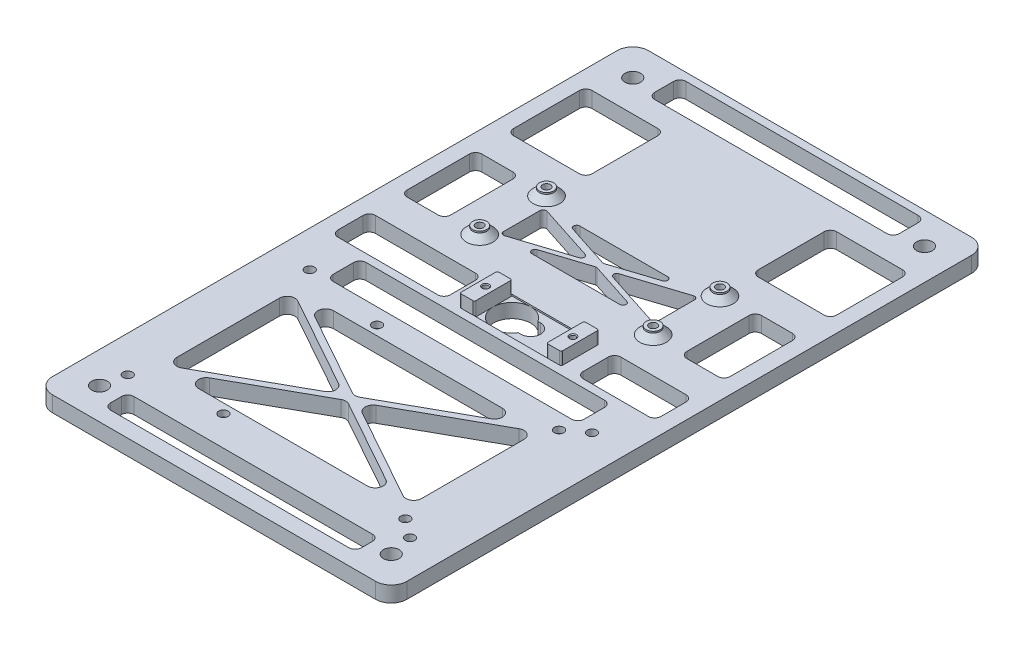
SolidWorks part; units mm, degrees
ref_plane "Front Plane" through (0, 0, 0) normal (0, 0, 1) x (1, 0, 0)
ref_plane "Top Plane" through (0, 0, 0) normal (0, 1, 0) x (1, 0, 0)
ref_plane "Right Plane" through (0, 0, 0) normal (1, 0, 0) x (0, 0, -1)
sketch "Sketch1" plane through (0, 0, 0) normal (0, 1, 0) x (1, 0, 0)
  line L0 (-56.5, -95) -> (-56.5, 95)
  line L1 (-46.5, -85) -> (46.5, -85) construction
  line L2 (-46.5, -85) -> (-46.5, 85) construction
  line L3 (-46.5, 85) -> (46.5, 85) construction
  line L4 (46.5, -85) -> (46.5, 85) construction
  line L5 (-46.5, -85) -> (46.5, 85) construction
  line L6 (-46.5, 85) -> (46.5, -85) construction
  line L7 (-56.5, 95) -> (56.5, 95)
  line L8 (56.5, -95) -> (56.5, 95)
  line L9 (-56.5, -95) -> (56.5, -95)
  circle A0 centre (46.5, 85) radius 2.5
  circle A1 centre (-46.5, 85) radius 2.5
  circle A2 centre (-46.5, -85) radius 2.5
  circle A3 centre (46.5, -85) radius 2.5
  point P0 (0, 0)
  dimension "D3" = 5
  dimension "D1" = 170
  dimension "D2" = 93
  dimension "D4" = 10
extrude "Boss-Extrude1" add sketch "Sketch1" along normal blind 5
fillet "Fillet1" radius 5 4 edges at (-56.5, 2.5, 95) (-56.5, 2.5, -95) (56.5, 2.5, -95) (56.5, 2.5, 95)
sketch "Sketch2" plane through (0, 5, 0) normal (0, 1, 0) x (1, 0, 0)
  line L0 (-39, -24) -> (-39, -73) construction
  line L1 (-39, -24) -> (39, -24) construction
  line L2 (-39, -20.5) -> (39, -20.5) construction
  line L3 (42.5, -48.5) -> (-39, -48.5) construction
  line L4 (-42.5, -24) -> (-42.5, -73) construction
  line L5 (42.5, -24) -> (42.5, -73) construction
  line L6 (-39, -76.5) -> (39, -76.5) construction
  line L7 (0, -20.5) -> (0, -1.8528) construction
  line L8 (-51.5, -95) -> (51.5, -95) construction
  circle A0 centre (39, -24) radius 1.5
  circle A1 centre (39, -73) radius 1.5
  arc A2 (-39, -20.5) -> (-42.5, -24) centre (-39, -24) ccw construction
  arc A3 (-39, -76.5) -> (-42.5, -73) centre (-39, -73) cw construction
  arc A4 (42.5, -24) -> (39, -20.5) centre (39, -24) ccw construction
  arc A5 (42.5, -73) -> (39, -76.5) centre (39, -73) cw construction
  circle A6 centre (-19, -24) radius 1.5
  circle A7 centre (-19, -73) radius 1.5
  point P14 (1.75, -48.5)
  dimension "D1" = 3
  dimension "D2" = 49
  dimension "D3" = 85
  dimension "D4" = 56
  dimension "D5" = 58
  dimension "D6" = 18.5
extrude "Cut-Extrude1" cut sketch "Sketch2" against normal blind 10
sketch "Sketch3" plane through (0, 5, 0) normal (0, 1, 0) x (1, 0, 0)
  line L0 (-45, -80) -> (45, -80) construction
  line L1 (-47.5, -77.5) -> (-47.5, -19.5) construction
  line L2 (-45, -17) -> (45, -17) construction
  line L3 (47.5, -77.5) -> (47.5, -19.5) construction
  line L4 (-47.5, -80) -> (47.5, -17) construction
  line L5 (-47.5, -17) -> (47.5, -80) construction
  line L6 (-51.5, -95) -> (51.5, -95) construction
  circle A0 centre (45, -19.5) radius 1.5
  circle A1 centre (45, -77.5) radius 1.5
  circle A2 centre (-45, -19.5) radius 1.5
  circle A3 centre (-45, -77.5) radius 1.5
  arc A4 (-47.5, -19.5) -> (-45, -17) centre (-45, -19.5) cw construction
  arc A5 (-45, -80) -> (-47.5, -77.5) centre (-45, -77.5) cw construction
  arc A6 (45, -80) -> (47.5, -77.5) centre (45, -77.5) ccw construction
  arc A7 (45, -17) -> (47.5, -19.5) centre (45, -19.5) cw construction
  point P0 (0, -48.5)
  dimension "D3" = 2.5
  dimension "D1" = 95
  dimension "D2" = 63
  dimension "D4" = 15
extrude "Cut-Extrude2" cut sketch "Sketch3" against normal blind 10
sketch "Sketch5" plane through (0, 5, 0) normal (0, 1, 0) x (1, 0, 0)
  line L1 (-38, -90) -> (38, -90)
  line L2 (-40, -88) -> (-40, -84.5)
  line L3 (-38, -82.5) -> (38, -82.5)
  line L4 (40, -88) -> (40, -84.5)
  line L5 (-40, -90) -> (40, -82.5) construction
  line L6 (-40, -82.5) -> (40, -90) construction
  circle A2 centre (-46.5, -85) radius 2.5 construction
  arc A3 (-38, -90) -> (-40, -88) centre (-38, -88) cw
  arc A4 (-40, -84.5) -> (-38, -82.5) centre (-38, -84.5) cw
  arc A5 (38, -82.5) -> (40, -84.5) centre (38, -84.5) cw
  arc A6 (38, -90) -> (40, -88) centre (38, -88) ccw
  point P0 (0, -86.25)
  dimension "D3" = 2
  dimension "D1" = 7.5
  dimension "D2" = 80
extrude "Cut-Extrude4" cut sketch "Sketch5" against normal blind 10
sketch "Sketch21" plane through (0, 5, 0) normal (0, 1, 0) x (1, 0, 0)
  line L4 (5.975, 2.875) -> (5.122, 2.875) construction
  line L5 (5.975, -2.875) -> (5.122, -2.875) construction
  line L6 (5.975, -3.125) -> (5.122, -3.125)
  line L7 (5.975, 3.125) -> (5.122, 3.125)
  arc A8 (4.9085, 2.9948) -> (4.9085, -2.9948) centre (0, 0) ccw construction
  arc A11 (5.975, -2.875) -> (5.975, 2.875) centre (5.975, 0) ccw construction
  arc A12 (4.9085, 2.9948) -> (5.122, 2.875) centre (5.122, 3.125) ccw construction
  arc A13 (5.122, -2.875) -> (4.9085, -2.9948) centre (5.122, -3.125) ccw construction
  arc A14 (5.122, 3.125) -> (5.122, -3.125) centre (0, 0) ccw
  arc A15 (5.122, -3.125) -> (5.122, -3.125) centre (5.122, -3.125) ccw
  arc A16 (5.975, -3.125) -> (5.975, 3.125) centre (5.975, 0) ccw
  arc A17 (5.122, 3.125) -> (5.122, 3.125) centre (5.122, 3.125) ccw
  dimension "D2" = 2.875
  dimension "D3" = 5.75
  dimension "D4" = 0.25
  dimension "D5" = 0.25
  dimension "D1" = 5.975
extrude "Cut-Extrude16" cut sketch "Sketch21" against normal through all
sketch "Sketch22" plane through (0, 5, 0) normal (0, 1, 0) x (1, 0, 0)
  line L0 (-6, 6) -> (-6, -6)
  line L1 (-6, 6) -> (17, 6)
  line L2 (-6, -6) -> (17, -6)
  line L3 (17, 6) -> (17, -6)
  arc A0 (5.122, 3.125) -> (5.122, -3.125) centre (0, 0) ccw construction
  dimension "D1" = 23
extrude "Cut-Extrude17" cut sketch "Sketch22" against normal blind 0.5
sketch "Sketch23" plane through (0, 5, 0) normal (0, 1, 0) x (1, 0, 0)
  line L0 (-6, 6) -> (-6, -6)
  line L1 (-6, 6) -> (-10.675, 6)
  line L2 (-6, -6) -> (-10.675, -6)
  line L3 (-10.675, 6) -> (-10.675, -6)
  line L4 (5.5, -6) -> (5.5, 6) construction
  line L5 (-6, -6) -> (17, -6) construction
  line L6 (17, 6) -> (-6, 6) construction
  line L7 (17, -6) -> (21.675, -6)
  line L8 (21.675, 6) -> (21.675, -6)
  line L9 (17, 6) -> (21.675, 6)
  line L10 (17, 6) -> (17, -6)
  circle A0 centre (-8.4, 0) radius 0.875
  circle A1 centre (19.4, 0) radius 0.875
  dimension "D2" = 1.75
  dimension "D1" = 4.675
  dimension "D3" = 2.4
extrude "Boss-Extrude5" add sketch "Sketch23" along normal blind 4
sketch "Sketch24" plane through (0, 5, 0) normal (0, 1, 0) x (1, 0, 0)
  circle A0 centre (19.4, 0) radius 0.875 construction
  circle A1 centre (-8.4, 0) radius 0.875 construction
  circle A2 centre (19.4, 0) radius 0.875
  circle A3 centre (-8.4, 0) radius 0.875
extrude "Cut-Extrude18" cut sketch "Sketch24" against normal blind 1.5
sketch "Sketch9" plane through (0, 5, 0) normal (0, 1, 0) x (1, 0, 0)
  line L0 (-48.1787, 10) -> (48.1787, 10)
  line L1 (-50, 11.8213) -> (-50, 38.1787)
  line L2 (-48.1787, 40) -> (48.1787, 40)
  line L3 (50, 11.8213) -> (50, 38.1787)
  line L4 (-50, 10) -> (50, 40) construction
  line L5 (-50, 40) -> (50, 10) construction
  arc A0 (48.1787, 40) -> (50, 38.1787) centre (48.1787, 38.1787) cw
  arc A1 (48.1787, 10) -> (50, 11.8213) centre (48.1787, 11.8213) ccw
  arc A2 (-48.1787, 10) -> (-50, 11.8213) centre (-48.1787, 11.8213) cw
  arc A3 (-50, 38.1787) -> (-48.1787, 40) centre (-48.1787, 38.1787) cw
  point P0 (0, 25)
  dimension "D4" = 1.8213
  dimension "D1" = 30
  dimension "D2" = 100
  dimension "D3" = 25
sketch "Sketch12" plane through (0, 5, 0) normal (0, 1, 0) x (1, 0, 0)
  line L1 (-51.5, 75) -> (-26.5, 75)
  line L2 (-51.5, 75) -> (-51.5, 50)
  line L3 (-51.5, 50) -> (-26.5, 50)
  line L4 (-26.5, 75) -> (-26.5, 50)
  line L6 (0, 0) -> (0, -22.2555) construction
  line L7 (26.5, 75) -> (26.5, 50)
  line L8 (51.5, 50) -> (26.5, 50)
  line L9 (51.5, 75) -> (51.5, 50)
  line L10 (51.5, 75) -> (26.5, 75)
  line L11 (-56.5, 90) -> (-56.5, -90) construction
  dimension "D1" = 25
  dimension "D2" = 25
  dimension "D3" = 50
  dimension "D4" = 5
extrude "Cut-Extrude9" cut sketch "Sketch12" against normal through all
sketch "Sketch15" plane through (0, 5, 0) normal (0, 1, 0) x (1, 0, 0)
  line L1 (-51.5, 6) -> (-15.675, 6)
  line L2 (-51.5, 6) -> (-51.5, -6)
  line L3 (-51.5, -6) -> (-15.675, -6)
  line L4 (-15.675, 6) -> (-15.675, -6)
  line L6 (-56.5, 90) -> (-56.5, -90) construction
  line L9 (26.675, 6) -> (51.5, 6)
  line L10 (26.675, 6) -> (26.675, -6)
  line L11 (26.675, -6) -> (51.5, -6)
  line L12 (51.5, 6) -> (51.5, -6)
  line L13 (56.5, -90) -> (56.5, 90) construction
  line L15 (17, 6) -> (-6, 6) construction
  line L16 (-6, -6) -> (17, -6) construction
  line L17 (21.675, -6) -> (21.675, 6) construction
  line L18 (-10.675, 6) -> (-10.675, -6) construction
  dimension "D1" = 5
  dimension "D2" = 5
  dimension "D3" = 5
  dimension "D4" = 5
extrude "Cut-Extrude11" cut sketch "Sketch15" against normal up to next
fillet "Fillet3" radius 2 16 edges at (-51.5, 2.5, 6) (-51.5, 2.5, -6) (-15.675, 2.5, -6) (-15.675, 2.5, 6) (51.5, 2.5, -6) (26.675, 2.5, -6) (26.675, 2.5, 6) (51.5, 2.5, 6) (51.5, 2.5, -50) (51.5, 2.5, -75) (26.5, 2.5, -50) (26.5, 2.5, -75) (-26.5, 2.5, -50) (-51.5, 2.5, -50) (-51.5, 2.5, -75) (-26.5, 2.5, -75)
sketch "Sketch16" plane through (0, 0, 0) normal (0, -1, 0) x (1, 0, 0)
  line L0 (-42, 64.8229) -> (-42, 32.1771)
  line L1 (-42.5, 70.5) -> (36.5, 70.5) construction
  line L2 (-42.5, 70.5) -> (-42.5, 26.5) construction
  line L3 (-42.5, 26.5) -> (36.5, 26.5) construction
  line L4 (36.5, 70.5) -> (36.5, 26.5) construction
  line L5 (-42.5, 70.5) -> (36.5, 26.5) construction
  line L6 (-42.5, 26.5) -> (36.5, 70.5) construction
  line L7 (-38.2835, 29.993) -> (-8.9766, 46.3159)
  line L8 (-8.9766, 50.6841) -> (-38.2835, 67.007)
  line L9 (-31.1371, 31.6841) -> (-4.2165, 46.6778)
  line L10 (-1.7835, 46.6778) -> (25.1371, 31.6841)
  line L11 (23.9206, 27) -> (-29.9206, 27)
  line L12 (-3, 48.5) -> (-3, 70.5) construction
  line L13 (-3, 48.5) -> (36.5, 48.5) construction
  line L14 (32.2835, 29.993) -> (2.9766, 46.3159)
  line L15 (36, 64.8229) -> (36, 32.1771)
  line L16 (2.9766, 50.6841) -> (32.2835, 67.007)
  line L17 (-1.7835, 50.3222) -> (25.1371, 65.3159)
  line L18 (-31.1371, 65.3159) -> (-4.2165, 50.3222)
  line L19 (23.9206, 70) -> (-29.9206, 70)
  line L20 (-33.5875, -28) -> (-33.5875, -6) construction
  line L26 (-27.65, -38.65) -> (27.65, -38.65) construction
  line L27 (-27.65, -38.65) -> (-27.65, -17.35) construction
  line L28 (-49.5, -6) -> (-17.675, -6) construction
  line L29 (-33.5875, -28) -> (-33.5875, -50) construction
  line L30 (51.5, -95) -> (-51.5, -95) construction
  line L31 (-37, -82.5) -> (37, -82.5)
  line L32 (-39, -84.5) -> (-39, -90.5)
  line L33 (-37, -92.5) -> (37, -92.5)
  line L34 (39, -84.5) -> (39, -90.5)
  line L35 (-39, -82.5) -> (39, -92.5) construction
  line L36 (-39, -92.5) -> (39, -82.5) construction
  line L37 (-28.5, -75) -> (-49.5, -75) construction
  line L44 (-49.5, -50) -> (-28.5, -50) construction
  line L63 (-27.65, -17.35) -> (27.65, -17.35) construction
  line L64 (27.65, -38.65) -> (27.65, -17.35) construction
  line L65 (-27.65, -38.65) -> (27.65, -17.35) construction
  line L66 (-27.65, -17.35) -> (27.65, -38.65) construction
  circle A0 centre (-45, 77.5) radius 1.5 construction
  circle A1 centre (39, 73) radius 1.5 construction
  circle A2 centre (39, 24) radius 1.5 construction
  circle A3 centre (-19, 73) radius 1.5 construction
  arc A4 (23.9206, 27) -> (25.1371, 31.6841) centre (23.9206, 29.5) ccw
  arc A5 (-1.7835, 46.6778) -> (-4.2165, 46.6778) centre (-3, 44.4938) ccw
  arc A6 (-29.9206, 27) -> (-31.1371, 31.6841) centre (-29.9206, 29.5) cw
  arc A7 (-42, 32.1771) -> (-38.2835, 29.993) centre (-39.5, 32.1771) ccw
  arc A8 (-8.9766, 46.3159) -> (-8.9766, 50.6841) centre (-10.193, 48.5) ccw
  arc A9 (-38.2835, 67.007) -> (-42, 64.8229) centre (-39.5, 64.8229) ccw
  arc A10 (36, 32.1771) -> (32.2835, 29.993) centre (33.5, 32.1771) cw
  arc A11 (2.9766, 46.3159) -> (2.9766, 50.6841) centre (4.193, 48.5) cw
  arc A12 (32.2835, 67.007) -> (36, 64.8229) centre (33.5, 64.8229) cw
  arc A13 (-1.7835, 50.3222) -> (-4.2165, 50.3222) centre (-3, 52.5062) cw
  arc A14 (23.9206, 70) -> (25.1371, 65.3159) centre (23.9206, 67.5) cw
  arc A15 (-29.9206, 70) -> (-31.1371, 65.3159) centre (-29.9206, 67.5) ccw
  circle A16 centre (-46.5, -85) radius 2.5 construction
  circle A17 centre (46.5, -85) radius 2.5 construction
  arc A30 (-39, -90.5) -> (-37, -92.5) centre (-37, -90.5) ccw
  arc A31 (37, -92.5) -> (39, -90.5) centre (37, -90.5) ccw
  arc A32 (39, -84.5) -> (37, -82.5) centre (37, -84.5) ccw
  arc A33 (-37, -82.5) -> (-39, -84.5) centre (-37, -84.5) ccw
  circle A34 centre (-27.65, -17.35) radius 1.25
  circle A35 centre (27.65, -17.35) radius 1.25
  circle A36 centre (27.65, -38.65) radius 1.25
  circle A37 centre (-27.65, -38.65) radius 1.25
  point P4 (-3, 48.5)
  point P52 (0, -28)
  point P69 (0, -87.5)
  dimension "D3" = 2.5
  dimension "D4" = 2.5
  dimension "D11" = 2.5
  dimension "D18" = 2
  dimension "D19" = 2
  dimension "D20" = 2.5
  dimension "D1" = 2.5
  dimension "D2" = 2.5
  dimension "D5" = 1
  dimension "D6" = 1
  dimension "D7" = 1
  dimension "D8" = 1
  dimension "D9" = 1
  dimension "D10" = 1
  dimension "D12" = 55.3
  dimension "D13" = 21.3
  dimension "D14" = 2.5
  dimension "D15" = 7.5
  dimension "D16" = 7.5
  dimension "D17" = 7.5
extrude "Cut-Extrude12" cut sketch "Sketch16" against normal up to next
sketch "Sketch17" plane through (0, 5, 0) normal (0, 1, 0) x (1, 0, 0)
  line L0 (0, 0) -> (0, 50000) construction
  line L1 (-39.65, 39.9) -> (-49.5, 39.9)
  line L2 (-37.65, 37.9) -> (-37.65, 18.1)
  line L3 (-39.65, 16.1) -> (-49.5, 16.1)
  line L4 (-51.5, 37.9) -> (-51.5, 18.1)
  line L5 (-37.65, 39.9) -> (-51.5, 16.1) construction
  line L6 (-37.65, 16.1) -> (-51.5, 39.9) construction
  line L7 (-51.5, 73) -> (-51.5, 52) construction
  line L8 (39.65, 16.1) -> (49.5, 16.1)
  line L9 (51.5, 37.9) -> (51.5, 18.1)
  line L10 (39.65, 39.9) -> (49.5, 39.9)
  line L11 (37.65, 37.9) -> (37.65, 18.1)
  circle A0 centre (-27.65, 17.35) radius 1.25 construction
  circle A1 centre (-27.65, 38.65) radius 1.25 construction
  arc A2 (-51.5, 18.1) -> (-49.5, 16.1) centre (-49.5, 18.1) ccw
  arc A3 (-39.65, 16.1) -> (-37.65, 18.1) centre (-39.65, 18.1) ccw
  arc A4 (-37.65, 37.9) -> (-39.65, 39.9) centre (-39.65, 37.9) ccw
  arc A5 (-49.5, 39.9) -> (-51.5, 37.9) centre (-49.5, 37.9) ccw
  arc A6 (51.5, 18.1) -> (49.5, 16.1) centre (49.5, 18.1) cw
  arc A7 (49.5, 39.9) -> (51.5, 37.9) centre (49.5, 37.9) cw
  arc A8 (39.65, 16.1) -> (37.65, 18.1) centre (39.65, 18.1) cw
  arc A9 (37.65, 37.9) -> (39.65, 39.9) centre (39.65, 37.9) cw
  point P4 (-44.575, 28)
  dimension "D2" = 2
  dimension "D1" = 10
extrude "Cut-Extrude13" cut sketch "Sketch17" against normal up to next
sketch "Sketch18" plane through (0, 5, 0) normal (0, 1, 0) x (1, 0, 0)
  line L0 (-24.65, 33.5615) -> (-24.65, 21.9129)
  line L1 (-25.15, 36.15) -> (25.15, 36.15) construction
  line L2 (-25.15, 36.15) -> (-25.15, 19.85) construction
  line L3 (-25.15, 19.85) -> (25.15, 19.85) construction
  line L4 (25.15, 36.15) -> (25.15, 19.85) construction
  line L5 (-25.15, 36.15) -> (25.15, 19.85) construction
  line L6 (-25.15, 19.85) -> (25.15, 36.15) construction
  line L7 (-23.3417, 20.9616) -> (-5.3685, 26.7859)
  line L8 (-5.3685, 28.6885) -> (-23.3417, 34.5128)
  line L9 (-14.0334, 35.65) -> (14.0334, 35.65)
  line L10 (14.3417, 33.6987) -> (0.3083, 29.1511)
  line L11 (-0.3083, 29.1511) -> (-14.3417, 33.6987)
  line L12 (0, 28) -> (0, 19.85) construction
  line L13 (0, 28) -> (25.15, 28) construction
  line L14 (23.3417, 20.9616) -> (5.3685, 26.7859)
  line L15 (24.65, 33.5615) -> (24.65, 21.9129)
  line L16 (5.3685, 28.6885) -> (23.3417, 34.5128)
  line L17 (14.3417, 22.3013) -> (0.3083, 26.8489)
  line L18 (-14.0334, 20.35) -> (14.0334, 20.35)
  line L19 (-0.3083, 26.8489) -> (-14.3417, 22.3013)
  line L20 (-49.5, -6) -> (-17.675, -6) construction
  line L21 (-38, -8.5) -> (38, -8.5)
  line L22 (-40, -10.5) -> (-40, -17)
  line L23 (-38, -19) -> (38, -19)
  line L24 (40, -10.5) -> (40, -17)
  line L25 (-40, -8.5) -> (40, -19) construction
  line L26 (-40, -19) -> (40, -8.5) construction
  circle A0 centre (-27.65, 38.65) radius 1.25 construction
  circle A1 centre (-27.65, 17.35) radius 1.25 construction
  circle A2 centre (27.65, 38.65) radius 1.25 construction
  arc A3 (-0.3083, 29.1511) -> (0.3083, 29.1511) centre (0, 30.1024) ccw
  arc A4 (14.3417, 33.6987) -> (14.0334, 35.65) centre (14.0334, 34.65) ccw
  arc A5 (-14.0334, 35.65) -> (-14.3417, 33.6987) centre (-14.0334, 34.65) ccw
  arc A6 (-24.65, 21.9129) -> (-23.3417, 20.9616) centre (-23.65, 21.9129) ccw
  arc A7 (-5.3685, 26.7859) -> (-5.3685, 28.6885) centre (-5.6768, 27.7372) ccw
  arc A8 (-23.3417, 34.5128) -> (-24.65, 33.5615) centre (-23.65, 33.5615) ccw
  arc A9 (24.65, 21.9129) -> (23.3417, 20.9616) centre (23.65, 21.9129) cw
  arc A10 (5.3685, 26.7859) -> (5.3685, 28.6885) centre (5.6768, 27.7372) cw
  arc A11 (23.3417, 34.5128) -> (24.65, 33.5615) centre (23.65, 33.5615) cw
  arc A12 (14.3417, 22.3013) -> (14.0334, 20.35) centre (14.0334, 21.35) cw
  arc A13 (-0.3083, 26.8489) -> (0.3083, 26.8489) centre (0, 25.8976) cw
  arc A14 (-14.0334, 20.35) -> (-14.3417, 22.3013) centre (-14.0334, 21.35) cw
  circle A15 centre (-45, -19.5) radius 1.5 construction
  circle A16 centre (45, -19.5) radius 1.5 construction
  circle A17 centre (39, -24) radius 1.5 construction
  arc A18 (38, -8.5) -> (40, -10.5) centre (38, -10.5) cw
  arc A19 (40, -17) -> (38, -19) centre (38, -17) cw
  arc A20 (-38, -19) -> (-40, -17) centre (-38, -17) cw
  arc A21 (-38, -8.5) -> (-40, -10.5) centre (-38, -10.5) ccw
  point P4 (0, 28)
  point P54 (0, -13.75)
  dimension "D11" = 1
  dimension "D13" = 5
  dimension "D16" = 2
  dimension "D1" = 2.5
  dimension "D2" = 2.5
  dimension "D3" = 2.5
  dimension "D4" = 2.5
  dimension "D5" = 1
  dimension "D6" = 1
  dimension "D7" = 1
  dimension "D8" = 1
  dimension "D9" = 1
  dimension "D10" = 1
  dimension "D12" = 5
  dimension "D14" = 5
  dimension "D15" = 2.5
extrude "Cut-Extrude14" cut sketch "Sketch18" against normal through all
sketch "Sketch19" plane through (0, 5, 0) normal (0, 1, 0) x (1, 0, 0)
  circle A0 centre (-27.65, 17.35) radius 1.25 construction
  circle A1 centre (27.65, 17.35) radius 1.25 construction
  circle A2 centre (27.65, 38.65) radius 1.25 construction
  circle A3 centre (-27.65, 38.65) radius 1.25 construction
  circle A4 centre (-27.65, 17.35) radius 1.25
  circle A5 centre (27.65, 17.35) radius 1.25
  circle A6 centre (27.65, 38.65) radius 1.25
  circle A7 centre (-27.65, 38.65) radius 1.25
  circle A8 centre (-27.65, 38.65) radius 2.25
  circle A9 centre (-27.65, 17.35) radius 2.25
  circle A10 centre (27.65, 38.65) radius 2.25
  circle A11 centre (27.65, 17.35) radius 2.25
  dimension "D1" = 1
  dimension "D2" = 1
  dimension "D3" = 1
  dimension "D4" = 1
extrude "Boss-Extrude4" add sketch "Sketch19" along normal blind 2.5
chamfer "Chamfer1" distance 2 angle 45 4 edges at (-27.65, 5, -36.4) (-27.65, 5, -15.1) (27.65, 5, -15.1) (27.65, 5, -36.4)
sketch "Sketch20" plane through (0, 0, 0) normal (0, -1, 0) x (1, 0, 0)
  circle A0 centre (-19, 73) radius 2.5
  circle A1 centre (-19, 24) radius 2.5
  circle A2 centre (39, 24) radius 2.5
  circle A4 centre (39, 73) radius 2.5
  dimension "D1" = 5
extrude "Cut-Extrude15" cut sketch "Sketch20" against normal blind 3
fillet "Fillet4" radius 0.5 8 edges at (21.675, 7, -6) (17, 7, -6) (-10.675, 7, -6) (-6, 7, -6) (17, 7, 6) (-6, 7, 6) (21.675, 7, 6) (-10.675, 7, 6)
chamfer "Chamfer2" distance 0.25 angle 45 2 edges at (-8.4, 9, 0.875) (19.4, 9, -0.875)
